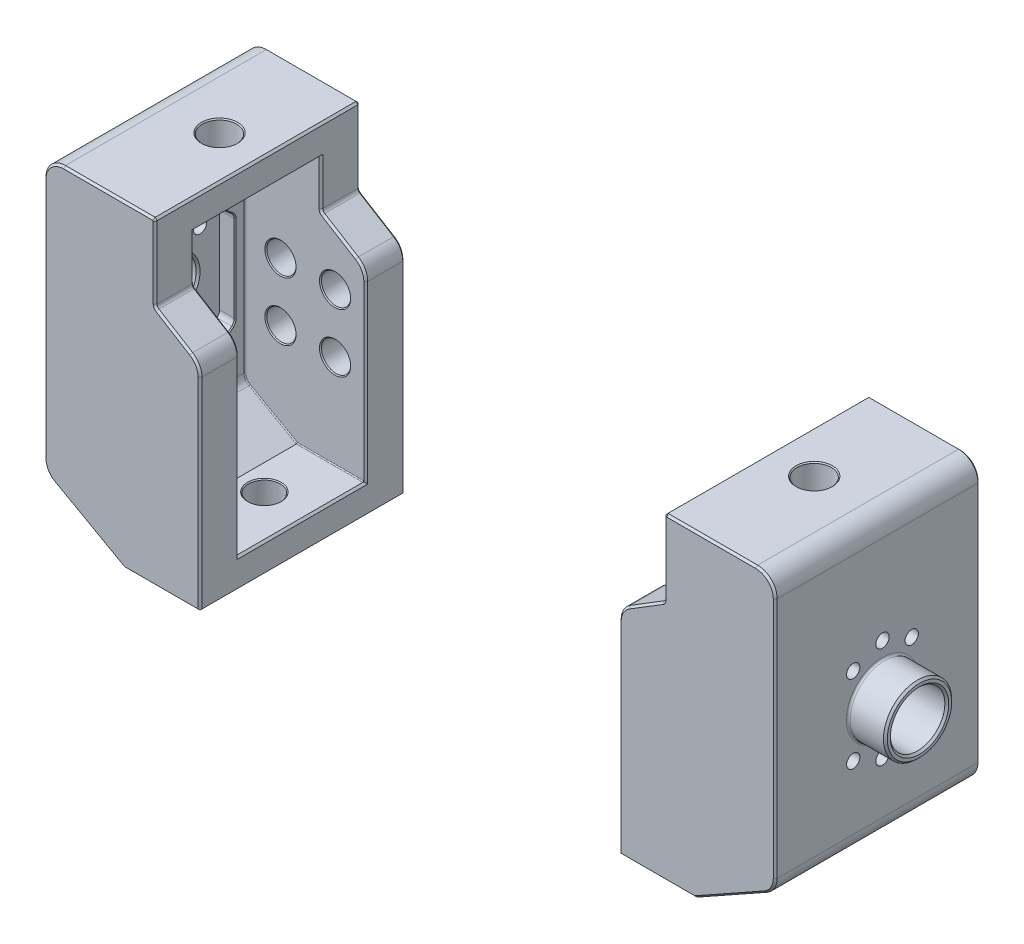
SolidWorks part; units mm, degrees
material "3.3549 (EN-AW 5182)"
ref_plane "Płaszczyzna przednia" through (0, 0, 0) normal (0, 0, 1) x (1, 0, 0)
ref_plane "Płaszczyzna górna" through (0, 0, 0) normal (0, 1, 0) x (1, 0, 0)
ref_plane "Płaszczyzna prawa" through (0, 0, 0) normal (1, 0, 0) x (0, 0, -1)
sketch "Szkic2" plane through (0, 0, 0) normal (0, 0, 1) x (1, 0, 0)
  line L0 (-74.8925, 20.1348) -> (-39, 0)
  line L14 (-23, 124.88) -> (-23, 163)
  line L15 (-23, 163) -> (-80, 163)
  line L16 (-80, 163) -> (-80, 28.8563)
  line L18 (-39, 0) -> (0, 0)
  line L19 (0, 0) -> (0, 104)
  line L20 (-4.7517, 112.5121) -> (-22.0497, 123.1776)
  arc A0 (-80, 28.8563) -> (-74.8925, 20.1348) centre (-70, 28.8563) ccw
  arc A6 (-23, 124.88) -> (-22.0497, 123.1776) centre (-21, 124.88) ccw
  arc A8 (0, 104) -> (-4.7517, 112.5121) centre (-10, 104) ccw
  point P9 (-80, 23)
  dimension "D3" = 10
  dimension "D11" = 10
  dimension "D9" = 2
  dimension "D1" = 163
  dimension "D2" = 140
  dimension "D4" = 39
  dimension "D5" = 104
  dimension "D6" = 38.12
  dimension "D7" = 57
  dimension "D8" = 80
  dimension "D10" = 0
extrude "Dodanie-wyciągnięcie1" add sketch "Szkic2" along normal blind 105
ref_plane "Płaszczyzna1" through (0, 0, 20) normal (0, 0, -1) x (-1, 0, 0)
sketch "Szkic3" plane through (0, 0, 20) normal (0, 0, -1) x (-1, 0, 0)
  line L0 (23, 163) -> (80, 163) construction
  line L1 (39, 0) -> (0, 0) construction
  line L2 (74.8925, 20.1348) -> (39, 0) construction
  line L5 (23, 124.88) -> (23, 163) construction
  line L6 (4.7517, 112.5121) -> (22.0497, 123.1776) construction
  line L7 (0, 0) -> (0, 104) construction
  line L8 (80, 163) -> (80, 28.8563) construction
  line L21 (62, 33.0296) -> (62, 148)
  line L22 (62, 148) -> (23, 148)
  line L23 (23, 148) -> (23, 124.88)
  line L24 (22.0497, 123.1776) -> (4.7517, 112.5121)
  line L25 (0, 104) -> (0, 15)
  line L26 (0, 15) -> (35.08, 15)
  line L27 (35.08, 15) -> (59.4463, 28.6689)
  arc A0 (22.0497, 123.1776) -> (23, 124.88) centre (21, 124.88) ccw construction
  arc A1 (4.7517, 112.5121) -> (0, 104) centre (10, 104) ccw
  arc A8 (59.4463, 28.6689) -> (62, 33.0296) centre (57, 33.0296) ccw
  arc A9 (22.0497, 123.1776) -> (23, 124.88) centre (21, 124.88) ccw
  dimension "D3" = 10
  dimension "D6" = 5
  dimension "D1" = 15
  dimension "D2" = 15
  dimension "D4" = 18
  dimension "D5" = 15
extrude "Wytnij-wyciągnięcie1" cut sketch "Szkic3" against normal blind 65
sketch "Szkic4" plane through (-80, 0, 0) normal (-1, 0, 0) x (0, 0, 1)
  line L0 (105, 163) -> (0, 163) construction
  line L1 (105, 163) -> (105, 28.8563) construction
  circle A0 centre (50, 81.5) radius 17.5
  dimension "D1" = 35
  dimension "D2" = 55
  dimension "81.5" = 81.5
extrude "Dodanie-wyciągnięcie2" add sketch "Szkic4" along normal blind 19
sketch "Szkic5" plane through (-99, 0, 0) normal (-1, 0, 0) x (0, 0, 1)
  circle A0 centre (50, 81.5) radius 14
  circle A1 centre (50, 81.5) radius 17.5 construction
  dimension "D1" = 28
extrude "Wytnij-wyciągnięcie2" cut sketch "Szkic5" against normal up to next
sketch "Szkic6" plane through (-99, 0, -93) normal (1, 0, 0) x (0, 0, -1)
  line L89 (-129.3105, 93.5237) -> (-127.1892, 91.4024)
  line L90 (-144.2, 98.4485) -> (-141.2, 98.4485)
  line L91 (-144.2, 98.4485) -> (-144.2, 95.4485)
  line L93 (-141.2, 98.4485) -> (-141.2, 95.4485)
  line L94 (-127.1892, 91.4024) -> (-129.3105, 89.281)
  line L95 (-129.3105, 93.5237) -> (-131.4318, 91.4024)
  line L96 (-122.2644, 79.5129) -> (-122.2644, 76.5129)
  line L97 (-122.2644, 76.5129) -> (-125.2644, 76.5129)
  line L98 (-122.2644, 79.5129) -> (-125.2644, 79.5129)
  line L99 (-127.1892, 64.6234) -> (-129.3105, 62.5021)
  line L100 (-129.3105, 62.5021) -> (-131.4318, 64.6234)
  line L101 (-127.1892, 64.6234) -> (-129.3105, 66.7447)
  line L102 (-141.2, 57.5773) -> (-144.2, 57.5773)
  line L103 (-144.2, 57.5773) -> (-144.2, 60.5773)
  line L104 (-141.2, 57.5773) -> (-141.2, 60.5773)
  line L105 (-156.0895, 62.5021) -> (-158.2108, 64.6234)
  line L106 (-158.2108, 64.6234) -> (-156.0895, 66.7447)
  line L107 (-156.0895, 62.5021) -> (-153.9682, 64.6234)
  line L108 (-163.1356, 76.5129) -> (-163.1356, 79.5129)
  line L109 (-163.1356, 79.5129) -> (-160.1356, 79.5129)
  line L110 (-163.1356, 76.5129) -> (-160.1356, 76.5129)
  line L111 (-158.2108, 91.4024) -> (-156.0895, 93.5237)
  line L112 (-156.0895, 93.5237) -> (-153.9682, 91.4024)
  line L113 (-158.2108, 91.4024) -> (-156.0895, 89.281)
  line L114 (-142.7, 78.0129) -> (-141.2, 95.4485) construction
  arc A27 (-131.4318, 91.4024) -> (-129.3105, 89.281) centre (-142.7, 78.0129) cw
  circle A36 centre (-143, 81.5) radius 14 construction
  arc A38 (-144.2, 95.4485) -> (-141.2, 95.4485) centre (-142.7, 78.0129) cw
  arc A39 (-125.2644, 79.5129) -> (-125.2644, 76.5129) centre (-142.7, 78.0129) cw
  arc A40 (-129.3105, 66.7447) -> (-131.4318, 64.6234) centre (-142.7, 78.0129) cw
  arc A41 (-141.2, 60.5773) -> (-144.2, 60.5773) centre (-142.7, 78.0129) cw
  arc A42 (-153.9682, 64.6234) -> (-156.0895, 66.7447) centre (-142.7, 78.0129) cw
  arc A43 (-160.1356, 76.5129) -> (-160.1356, 79.5129) centre (-142.7, 78.0129) cw
  arc A44 (-156.0895, 89.281) -> (-153.9682, 91.4024) centre (-142.7, 78.0129) cw
  dimension "D1" = 3
  dimension "D2" = 3
  dimension "D3" = 17.5
sketch "Szkic7" plane through (-62, 0, 0) normal (1, 0, 0) x (0, 0, -1)
  line L0 (0, 163) -> (0, 28.8563) construction
  line L1 (-71, 50) -> (-29, 50)
  line L2 (-76, 55) -> (-76, 120)
  line L3 (-71, 125) -> (-29, 125)
  line L4 (-24, 55) -> (-24, 120)
  line L5 (-76, 50) -> (-24, 125) construction
  line L6 (-76, 125) -> (-24, 50) construction
  arc A0 (-71, 50) -> (-76, 55) centre (-71, 55) cw
  arc A1 (-29, 50) -> (-24, 55) centre (-29, 55) ccw
  arc A2 (-29, 125) -> (-24, 120) centre (-29, 120) cw
  arc A3 (-76, 120) -> (-71, 125) centre (-71, 120) cw
  point P0 (-50, 87.5)
  dimension "D1" = 5
  dimension "D2" = 75
  dimension "D3" = 52
  dimension "D4" = 50
hole_wizard "Pogłębienie walcowe pod M8 Wkręt z łbem walcowym z gniazdem sześciokątnym1" positions "Szkic11" profile "Szkic12" counterbore size "M8" standard "ISO"
sketch "Szkic11" plane through (0, 0, 20) normal (0, 0, 1) x (1, 0, 0)
  line L0 (-23, 163) -> (-80, 163) construction
  point P0 (-43.7419, 93)
  point P2 (-15.7419, 93)
  point P4 (-43.7419, 63)
  point P6 (-15.7419, 63)
  dimension "D1" = 70
  dimension "D2" = 28
  dimension "D3" = 30
sketch "Szkic12" plane through (-43.7419, 93, 20) normal (1, 0, 0) x (0, -1, 0)
  line L0 (0, 0) -> (0, 50.2039)
  line L1 (0, 50.2039) -> (4.5, 47.5)
  line L2 (4.5, 47.5) -> (4.5, 8.6)
  line L3 (4.5, 8.6) -> (7.5, 8.6)
  line L4 (7.5, 8.6) -> (7.5, 0)
  line L5 (7.5, 0) -> (0, 0)
  line L10 (0, 50.2039) -> (-4.5, 47.5) construction
  line L11 (0, -6.35) -> (0, 107.95) construction
  dimension "Średnica otworu" = 9
  dimension "Głębokość otworu" = 47.5
  dimension "Średnica pogłębienia walcowego" = 15
  dimension "Głębokość pogłębienia walcowego" = 8.6
  dimension "Kąt wiertła" = 118
ref_plane "Płaszczyzna2" through (0, 0, 50) normal (0, 0, -1) x (-1, 0, 0)
sketch "Szkic13" plane through (0, 0, 50) normal (0, 0, -1) x (-1, 0, 0)
  line L0 (45, 167) -> (45, 148)
  line L1 (45, 167) -> (36, 167)
  line L2 (36, 167) -> (36.9, 148)
  line L3 (36.9, 148) -> (45, 148)
  line L4 (23, 124.88) -> (23, 163) construction
  line L5 (23, 163) -> (80, 163) construction
  point P6 (40.5, 167)
  dimension "D1" = 9
  dimension "D2" = 8.1
  dimension "D3" = 22
  dimension "D4" = 19
  dimension "D5" = 4
revolve "Wycięcie-obrót1" cut sketch "Szkic13" angle 360 about L0
sketch "Szkic14" plane through (0, 0, 50) normal (0, 0, -1) x (-1, 0, 0)
  line L0 (22, -4) -> (22, 15)
  line L1 (22, -4) -> (13, -4)
  line L2 (22, 15) -> (13.9, 15)
  line L3 (13.9, 15) -> (13, -4)
  line L5 (23, 124.88) -> (23, 163) construction
  line L6 (39, 0) -> (0, 0) construction
  point P2 (17.5, -4)
  dimension "D1" = 9
  dimension "D2" = 8.1
  dimension "D3" = 19
  dimension "D4" = 1
  dimension "D5" = 4
revolve "Wycięcie-obrót2" cut sketch "Szkic14" angle 360 about L0
ref_axis "Oś1" through (-45, 202.955, 50) along (0, -1, 0)
ref_axis "Oś2" through (-22, 0, 50) along (0, 1, 0)
fillet "Zaokrąglenie3" radius 10 1 edges at (-80, 163, 52.5)
chamfer "Sfazowanie3" distance 1 angle 45 12 edges at (-78.6292, 23.8028, 0) (-56.9463, 10.0674, 0) (-19.5, 0, 0) (0, 52, 0) (-1.2684, 108.8743, 0) (-13.4007, 117.8448, 0) (-22.7463, 123.9051, 0) (-23, 143.94, 0) (-46.5, 163, 0) (-77.0711, 160.0711, 0) (-80, 90.9281, 0) (-23, 163, 52.5)
chamfer "Sfazowanie4" distance 1 angle 45 12 edges at (-23, 143.44, 105) (-22.7463, 123.9051, 105) (-13.4007, 117.8448, 105) (-1.2684, 108.8743, 105) (0, 52, 105) (-19.5, 0, 105) (-56.9463, 10.0674, 105) (-78.6292, 23.8028, 105) (-80, 90.9281, 105) (-77.0711, 160.0711, 105) (-47, 163, 105) (-23.5, 162.5, 105)
chamfer "Sfazowanie6" distance 1 angle 45 1 edges at (0, 0, 52.5)
fillet "Zaokrąglenie4" radius 3 1 edges at (-39, 0, 52.5)
chamfer "Sfazowanie8" distance 1 angle 45 12 edges at (-23, 148, 52.5) (-23, 136.44, 20) (-22.7463, 123.9051, 20) (-13.4007, 117.8448, 20) (-1.2684, 108.8743, 20) (0, 59.5, 20) (0, 15, 52.5) (0, 59.5, 85) (-1.2684, 108.8743, 85) (-13.4007, 117.8448, 85) (-22.7463, 123.9051, 85) (-23, 136.44, 85)
fillet "Zaokrąglenie5" radius 0.5 11 edges at (-47.2631, 21.8344, 20) (-61.3146, 30.5028, 20) (-47.2631, 21.8344, 85) (-61.3146, 30.5028, 85) (-62, 90.5148, 20) (-43, 148, 20) (-62, 90.5148, 85) (-62, 148, 52.5) (-43, 148, 85) (-18.04, 15, 20) (-18.04, 15, 85)
chamfer "Sfazowanie13" distance 0.5 angle 45 4 edges at (-45, 148, 58.1) (-13.9, 15, 50) (-22, 0, 58.8105) (-45, 163, 41.1895) first distance on face at (-45, 148, 58.1) first distance on face at (-13.9, 15, 50) first distance on face at (-45, 163, 41.1895)
chamfer "Sfazowanie14" distance 0.5 angle 45 8 edges at (-8.2419, 63, 20) (-36.2419, 63, 20) (-8.2419, 93, 20) (-36.2419, 93, 20) (-11.2419, 63, 0) (-39.2419, 63, 0) (-39.2419, 93, 0) (-11.2419, 93, 0)
sketch "Szkic16" plane through (0, 0, 11.4) normal (0, 0, 1) x (1, 0, 0)
  circle A1 centre (-43.7419, 93) radius 7.5
  circle A2 centre (-43.7419, 93) radius 7.5
  circle A4 centre (-15.7419, 63) radius 7.5 construction
  circle A5 centre (-15.7419, 63) radius 4.5 construction
  circle A6 centre (-15.7419, 93) radius 4.5 construction
  circle A7 centre (-15.7419, 93) radius 7.5 construction
  circle A8 centre (-43.7419, 63) radius 7.5 construction
  circle A9 centre (-43.7419, 63) radius 4.5 construction
  circle A10 centre (-43.7419, 93) radius 4.5 construction
  circle A11 centre (-15.7419, 63) radius 7.5
  circle A12 centre (-15.7419, 63) radius 4.5
  circle A13 centre (-15.7419, 93) radius 4.5
  circle A14 centre (-15.7419, 93) radius 7.5
  circle A15 centre (-43.7419, 63) radius 7.5
  circle A16 centre (-43.7419, 63) radius 4.5
  circle A17 centre (-43.7419, 93) radius 4.5
  dimension "D1" = 0
extrude "Wytnij-wyciągnięcie8" cut sketch "Szkic16" against normal blind 2.5
sketch "Szkic17" plane through (-62, 0, 0) normal (1, 0, 0) x (0, 0, -1)
  line L0 (-75, 105.275) -> (-75, 57.725)
  line L1 (-25, 105.275) -> (-25, 57.725)
  circle A0 centre (-50, 81.5) radius 14 construction
  arc A12 (-75, 57.725) -> (-25, 57.725) centre (-50, 81.5) ccw
  arc A13 (-25, 105.275) -> (-75, 105.275) centre (-50, 81.5) ccw
  point P2 (-75, 81.5)
  dimension "D1" = 50
  dimension "D2" = 69
extrude "Wytnij-wyciągnięcie10" cut sketch "Szkic17" against normal blind 8
fillet "Zaokrąglenie8" radius 4 4 edges at (-66, 57.725, 75) (-66, 57.725, 25) (-66, 105.275, 25) (-66, 105.275, 75)
hole_wizard "Otwór gwintowany M81" positions "Szkic22" profile "Szkic23" tap size "M8" standard "ISO"
sketch "Szkic22" plane through (-70, 0, 0) normal (1, 0, 0) x (0, 0, -1)
  line L0 (-50, 95.5) -> (-50, 67.5) construction
  line L2 (-64, 81.5) -> (-36, 81.5) construction
  circle A0 centre (-50, 81.5) radius 14 construction
  point P0 (-65, 101.5)
  point P2 (-50, 107.5)
  point P4 (-35, 101.5)
  point P6 (-65, 61.5)
  point P8 (-50, 55.5)
  point P10 (-35, 61.5)
  dimension "D1" = 15
  dimension "D2" = 15
  dimension "D3" = 6
  dimension "D4" = 6
  dimension "D5" = 20
  dimension "D6" = 20
sketch "Szkic23" plane through (-70, 101.5, 65) normal (0, 1, 0) x (0, 0, -1)
  line L0 (0, 0) -> (0, 24.2929)
  line L1 (0, 24.2929) -> (3.4, 22.25)
  line L2 (3.4, 22.25) -> (3.4, 0)
  line L5 (3.4, 0) -> (0, 0)
  line L10 (0, 24.2929) -> (-3.4, 22.25) construction
  line L11 (0, -6.35) -> (0, 107.95) construction
  dimension "Średnica wiertła gwintu" = 6.8
  dimension "Głębokość otworu gwintowanego" = 22.25
  dimension "Kąt wiertła" = 118
cosmetic thread "Gwint otworu1" parameters "D1"=16, "D2"=8
cosmetic thread "Gwint otworu2" parameters "D1"=16, "D2"=8
cosmetic thread "Gwint otworu3" parameters "D1"=16, "D2"=8
cosmetic thread "Gwint otworu4" parameters "D1"=16, "D2"=8
cosmetic thread "Gwint otworu5" parameters "D1"=16, "D2"=8
cosmetic thread "Gwint otworu6" parameters "D1"=16, "D2"=8
chamfer "Sfazowanie15" distance 0.5 angle 45 8 edges at (-62, 57.8025, 74.6753) (-62, 47, 50) (-62, 57.8025, 25.3247) (-62, 81.5, 25) (-62, 105.1975, 25.3247) (-62, 116, 50) (-62, 105.1975, 74.6753) (-62, 81.5, 75)
fillet "Zaokrąglenie10" radius 1 1 edges at (-80, 99, 50)
chamfer "Sfazowanie16" distance 1 angle 45 3 edges at (-99, 67.5, 50) (-99, 64, 50) (-70, 95.5, 50)
ref_plane "Płaszczyzna3" through (107.5, 0, 0) normal (1, 0, 0) x (0, 0, -1)
mirror "Lustro2" about plane through (107.5, 0, 0) normal (1, 0, 0) of bodies 119
cosmetic thread "Gwint otworu7" parameters "D1"=16, "D2"=8
cosmetic thread "Gwint otworu8" parameters "D1"=16, "D2"=8
cosmetic thread "Gwint otworu9" parameters "D1"=16, "D2"=8
cosmetic thread "Gwint otworu10" parameters "D1"=16, "D2"=8
cosmetic thread "Gwint otworu11" parameters "D1"=16, "D2"=8
cosmetic thread "Gwint otworu12" parameters "D1"=16, "D2"=8
